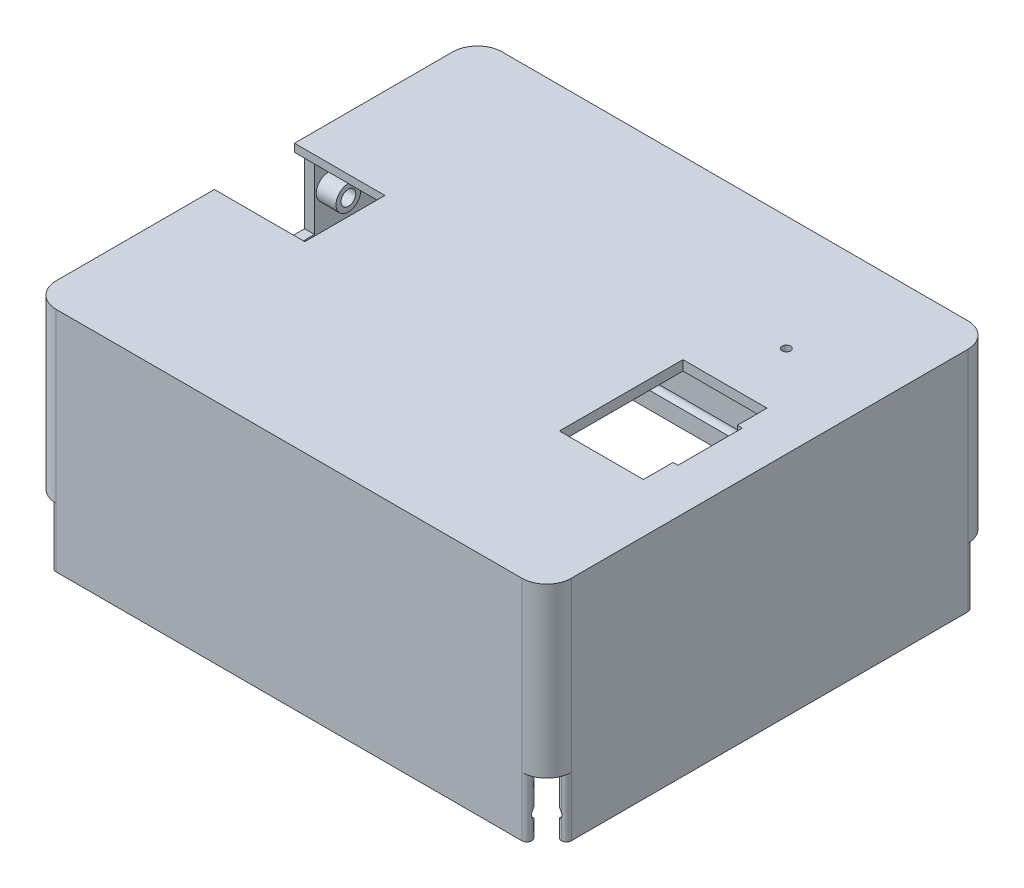
SolidWorks part; units mm, degrees
ref_plane "Plan de face" through (0, 0, 0) normal (0, 0, 1) x (1, 0, 0)
ref_plane "Plan de dessus" through (0, 0, 0) normal (0, 1, 0) x (1, 0, 0)
ref_plane "Plan de droite" through (0, 0, 0) normal (1, 0, 0) x (0, 0, -1)
sketch "Esquisse1" plane through (0, 0, 0) normal (0, 1, 0) x (1, 0, 0)
  line L1 (-52.1, -45.1) -> (52.1, -45.1)
  line L2 (-52.1, -45.1) -> (-52.1, 45.1)
  line L3 (-52.1, 45.1) -> (52.1, 45.1)
  line L4 (52.1, -45.1) -> (52.1, 45.1)
  line L5 (-52.1, -45.1) -> (52.1, 45.1) construction
  line L6 (-52.1, 45.1) -> (52.1, -45.1) construction
  point P0 (0, 0)
  dimension "D1" = 104.2
  dimension "D2" = 90.2
extrude "Boss.-Extru.1" add sketch "Esquisse1" along normal blind 2
sketch "Esquisse2" plane through (0, 0, 0) normal (0, -1, 0) x (1, 0, 0)
  line L8 (50.1, -43.1) -> (50.1, 43.1)
  line L9 (50.1, 43.1) -> (-50.1, 43.1)
  line L10 (-50.1, 43.1) -> (-50.1, -43.1)
  line L11 (-50.1, -43.1) -> (50.1, -43.1)
  line L12 (50.1, -43.1) -> (50.1, 43.1)
  line L13 (50.1, 43.1) -> (-50.1, 43.1)
  line L14 (-50.1, 43.1) -> (-50.1, -43.1)
  line L15 (-50.1, -43.1) -> (50.1, -43.1)
  line L16 (52.1, -45.1) -> (52.1, 45.1)
  line L17 (52.1, 45.1) -> (-52.1, 45.1)
  line L18 (-52.1, 45.1) -> (-52.1, -45.1)
  line L19 (-52.1, -45.1) -> (52.1, -45.1)
  line L20 (52.1, -45.1) -> (52.1, 45.1)
  line L21 (52.1, 45.1) -> (-52.1, 45.1)
  line L22 (-52.1, 45.1) -> (-52.1, -45.1)
  line L23 (-52.1, -45.1) -> (52.1, -45.1)
  dimension "D1" = 2
  dimension "D2" = 0
extrude "Boss.-Extru.2" add sketch "Esquisse2" along normal blind 44
sketch "Esquisse3" plane through (0, -44, 0) normal (0, -1, 0) x (1, 0, 0)
  line L0 (-50.1, 41.1) -> (-50.1, 43.1)
  line L1 (-52.1, 45.1) -> (-48.1, 45.1)
  line L2 (-52.1, 45.1) -> (-52.1, 41.1)
  line L3 (-52.1, 41.1) -> (-50.1, 41.1)
  line L4 (-48.1, 45.1) -> (-48.1, 43.1)
  line L5 (-50.1, 43.1) -> (-48.1, 43.1)
  dimension "D1" = 4
  dimension "D2" = 4
  dimension "D3" = 2
  dimension "D4" = 2
extrude "Enlèv. mat.-Extru.1" cut sketch "Esquisse3" against normal blind 12
mirror "Symétrie1" about plane through (0, 0, 0) normal (0, 0, 1) of "Enlèv. mat.-Extru.1"
mirror "Symétrie2" about plane through (0, 0, 0) normal (1, 0, 0) of "Symétrie1"
fillet "Congé3" radius 1 16 edges at (-48.1, -38, 45.1) (-48.1, -38, 43.1) (-50.1, -38, 41.1) (-52.1, -38, 41.1) (48.1, -38, 45.1) (48.1, -38, 43.1) (52.1, -38, 41.1) (50.1, -38, 41.1) (52.1, -38, -41.1) (50.1, -38, -41.1) (48.1, -38, -43.1) (48.1, -38, -45.1) (-48.1, -38, -45.1) (-48.1, -38, -43.1) (-50.1, -38, -41.1) (-52.1, -38, -41.1)
fillet "Congé1" radius 5 4 edges at (52.1, -15, 45.1) (52.1, -15, -45.1) (-52.1, -15, -45.1) (-52.1, -15, 45.1)
sketch "Esquisse4" plane through (0, 0, 0) normal (1, 0, 0) x (0, 0, -1)
  line L0 (-43.1, -32) -> (-43.1, -44) construction
  line L1 (-43.1, -38.4) -> (-43.1, -40.6)
  line L2 (-44.1, -44) -> (-43.1, -44) construction
  arc A1 (-43.1, -38.4) -> (-43.1, -40.6) centre (-43.1, -39.5) ccw
  dimension "D1" = 1.1
  dimension "D2" = 4.5
extrude "Enlèv. mat.-Extru.2" cut sketch "Esquisse4" against normal through all both and the other way through all
mirror "Symétrie4" about plane through (0, 0, 0) normal (0, 0, 1) of "Enlèv. mat.-Extru.2"
sketch "Esquisse5" plane through (0, 0, 0) normal (0, 0, 1) x (1, 0, 0)
  line L0 (-50.1, -32) -> (-50.1, -44) construction
  line L1 (-51.1, -44) -> (-50.1, -44) construction
  line L2 (-50.1, -38.4) -> (-50.1, -40.6)
  arc A0 (-50.1, -38.4) -> (-50.1, -40.6) centre (-50.1, -39.5) ccw
  dimension "D1" = 1.1
  dimension "D2" = 4.5
extrude "Enlèv. mat.-Extru.3" cut sketch "Esquisse5" against normal through all both and the other way through all
mirror "Symétrie5" about plane through (0, 0, 0) normal (1, 0, 0) of "Enlèv. mat.-Extru.3"
sketch "Esquisse6" plane through (-52.1, 0, 0) normal (-1, 0, 0) x (0, 0, 1)
  line L0 (0, 15.9382) -> (0, -19.3286) construction
  line L1 (-40.1, 2) -> (40.1, 2) construction
  line L2 (-10.15, -14) -> (10.15, -14)
  line L3 (-10.15, -14) -> (-10.15, 0)
  line L4 (-10.15, 0) -> (10.15, 0)
  line L5 (10.15, -14) -> (10.15, 0)
  line L6 (-10.15, -14) -> (10.15, 0) construction
  line L7 (-10.15, 0) -> (10.15, -14) construction
  point P3 (0, -7)
  dimension "D1" = 14
  dimension "D2" = 2
  dimension "D3" = 20.3
extrude "Enlèv. mat.-Extru.4" cut sketch "Esquisse6" against normal blind 5 and the other way through all
sketch "Esquisse7" plane through (-52.1, 0, 0) normal (-1, 0, 0) x (0, 0, 1)
  line L0 (0, 0) -> (0, 2) construction
  line L1 (-40.1, 2) -> (40.1, 2) construction
  line L3 (-8.1, 0) -> (8.1, 0)
  line L4 (-8.1, 0) -> (-8.1, 2)
  line L5 (-8.1, 2) -> (8.1, 2)
  line L6 (8.1, 0) -> (8.1, 2)
  line L7 (-8.1, 0) -> (8.1, 2) construction
  line L8 (-8.1, 2) -> (8.1, 0) construction
  point P7 (0, 1)
  dimension "D1" = 16.2
extrude "Enlèv. mat.-Extru.5" cut sketch "Esquisse7" against normal blind 18.3
sketch "Esquisse11" plane through (0, 0, 0) normal (0, 1, 0) x (1, 0, 0)
  line L0 (-52.1, 0) -> (-32.1, 0) construction
  line L1 (-52.1, 10.15) -> (-52.1, -10.15) construction
  line L3 (-52.1, 40.1) -> (-52.1, 8.1) construction
  line L4 (-52.1, -10.15) -> (-32.1, -10.15)
  line L5 (-52.1, -10.15) -> (-52.1, 10.15)
  line L6 (-52.1, 10.15) -> (-32.1, 10.15)
  line L7 (-32.1, -10.15) -> (-32.1, 10.15)
  line L8 (-52.1, -10.15) -> (-32.1, 10.15) construction
  line L9 (-52.1, 10.15) -> (-32.1, -10.15) construction
  point P6 (-42.1, 0)
  dimension "D1" = 20.3
  dimension "D2" = 20
extrude "Enlèv. mat.-Extru.8" cut sketch "Esquisse11" along normal blind 0.4
sketch "Esquisse15" plane through (0, -44, 0) normal (0, -1, 0) x (1, 0, 0)
  line L0 (-50.1, 40.1) -> (-50.1, -40.1) construction
  line L1 (50.3, -43.3) -> (-50.3, -43.3)
  line L2 (50.3, -43.3) -> (50.3, 43.3)
  line L3 (50.3, 43.3) -> (-50.3, 43.3)
  line L4 (-50.3, -43.3) -> (-50.3, 43.3)
  line L5 (50.3, -43.3) -> (-50.3, 43.3) construction
  line L6 (50.3, 43.3) -> (-50.3, -43.3) construction
  line L7 (47.1, 43.1) -> (-47.1, 43.1) construction
  point P0 (0, 0)
  dimension "D1" = 0.2
  dimension "D2" = 0.2
extrude "Enlèv. mat.-Extru.10" cut sketch "Esquisse15" against normal blind 4.5
sketch "Esquisse16" plane through (-52.1, 0, 0) normal (-1, 0, 0) x (0, 0, 1)
  circle A0 centre (-13, -7) radius 1.5
  dimension "D1" = 3
extrude "Enlèv. mat.-Extru.11" cut sketch "Esquisse16" against normal blind 4
mirror "Symétrie6" about plane through (0, 0, 0) normal (0, 0, 1) of "Enlèv. mat.-Extru.11"
sketch "Esquisse17" plane through (0, 2, 0) normal (0, 1, 0) x (1, 0, 0)
  line L0 (52.1, -40.1) -> (52.1, 40.1) construction
  line L1 (25.1, -15.5179) -> (42.1, -15.5179)
  line L2 (25.1, -15.5179) -> (25.1, 9.4821)
  line L3 (25.1, 9.4821) -> (42.1, 9.4821)
  line L4 (42.1, -15.5179) -> (42.1, 9.4821)
  line L5 (25.1, -15.5179) -> (42.1, 9.4821) construction
  line L6 (25.1, 9.4821) -> (42.1, -15.5179) construction
  point P0 (33.6, -3.0179)
  dimension "D1" = 25
  dimension "D2" = 17
  dimension "D3" = 10
extrude "Enlèv. mat.-Extru.12" cut sketch "Esquisse17" against normal up to next
sketch "Esquisse19" plane through (0, 0, 0) normal (0, -1, 0) x (1, 0, 0)
  line L0 (33.6, 19.5179) -> (33.6, -24.4821) construction
  line L8 (25.1, -9.4821) -> (25.1, 15.5179) construction
  line L9 (42.1, 15.5179) -> (42.1, -9.4821) construction
  line L10 (25.1, 15.5179) -> (42.1, 15.5179) construction
  line L11 (23.6, 7.9179) -> (46.6322, 7.9179) construction
  line L12 (42.1, -9.4821) -> (25.1, -9.4821) construction
  circle A0 centre (33.6, -21.8821) radius 0.85
  dimension "D1" = 1.7
  dimension "D2" = 1.5
  dimension "D5" = 7.6
  dimension "D7" = 12.4
extrude "Enlèv. mat.-Extru.13" cut sketch "Esquisse19" against normal blind 2
sketch "Esquisse20" plane through (-50.1, 0, 0) normal (1, 0, 0) x (0, 0, -1)
  circle A0 centre (-13, -7) radius 2.5
  circle A1 centre (13, -7) radius 2.5
  circle A2 centre (-13, -7) radius 1.5 construction
  circle A3 centre (-13, -7) radius 1.5
  circle A4 centre (13, -7) radius 1.5 construction
  circle A5 centre (13, -7) radius 1.5
  dimension "D1" = 5
  dimension "D2" = 5
extrude "Boss.-Extru.4" add sketch "Esquisse20" along normal blind 4
sketch "Esquisse21" plane through (0, 2, 0) normal (0, 1, 0) x (1, 0, 0)
  line L0 (25.1, -3.0179) -> (52.1, -3.0179) construction
  line L1 (25.1, 9.4821) -> (25.1, -15.5179) construction
  line L2 (52.1, -40.1) -> (52.1, 40.1) construction
  line L3 (42.1, -15.5179) -> (42.1, 9.4821) construction
  line L4 (43.1, -9.5179) -> (42.1, -9.5179)
  line L5 (43.1, -9.5179) -> (43.1, 3.4821)
  line L6 (43.1, 3.4821) -> (42.1, 3.4821)
  line L7 (42.1, -9.5179) -> (42.1, 3.4821)
  line L8 (43.1, -9.5179) -> (42.1, 3.4821) construction
  line L9 (43.1, 3.4821) -> (42.1, -9.5179) construction
  point P6 (42.6, -3.0179)
  dimension "D1" = 13
  dimension "D2" = 1
extrude "Enlèv. mat.-Extru.14" cut sketch "Esquisse21" against normal up to next
sketch "Esquisse22" plane through (0, 0, 0) normal (0, -1, 0) x (1, 0, 0)
  line L0 (33.6, 15.5179) -> (33.6, 26.6551) construction
  line L5 (25.1, 15.5179) -> (42.1, 15.5179) construction
  line L7 (21.6, 19.0179) -> (45.6, 19.0179)
  line L8 (21.6, 19.0179) -> (21.6, 21.0179)
  line L9 (21.6, 21.0179) -> (45.6, 21.0179)
  line L10 (45.6, 19.0179) -> (45.6, 21.0179)
  line L11 (21.6, 19.0179) -> (45.6, 21.0179) construction
  line L12 (21.6, 21.0179) -> (45.6, 19.0179) construction
  line L13 (21.6, 19.0179) -> (23, 19.0179)
  line L14 (21.6, 19.0179) -> (21.6, 13.5179)
  line L15 (21.6, 13.5179) -> (23, 13.5179)
  line L16 (23, 19.0179) -> (23, 13.5179)
  line L17 (45.6, 19.0179) -> (44.2, 19.0179)
  line L18 (45.6, 19.0179) -> (45.6, 13.5179)
  line L19 (45.6, 13.5179) -> (44.2, 13.5179)
  line L20 (44.2, 19.0179) -> (44.2, 13.5179)
  point P0 (33.6, 20.0179)
  dimension "D1" = 3.5
  dimension "D2" = 24
  dimension "D3" = 2
  dimension "D4" = 2
  dimension "D5" = 21.2
extrude "Boss.-Extru.5" add sketch "Esquisse22" along normal blind 2 contours L16 L7 L14 L15 | L7 L10 L9 L8 | L7 L20 L19 L18 region at (33.6, 0, 20.0179) region at (22.3, 0, 16.2679) region at (44.9, 0, 16.2679)
sketch "Esquisse25" plane through (0, -2, 0) normal (0, -1, 0) x (1, 0, 0)
  line L0 (25.1, 15.5179) -> (42.1, 15.5179) construction
  line L1 (21.6, 21.0179) -> (27.1, 21.0179)
  line L2 (21.6, 21.0179) -> (21.6, 13.5179)
  line L3 (21.6, 13.5179) -> (27.1, 13.5179)
  line L4 (27.1, 21.0179) -> (27.1, 13.5179)
  line L5 (33.6, 15.5179) -> (33.6, 10.1392) construction
  line L6 (45.6, 21.0179) -> (40.1, 21.0179)
  line L7 (45.6, 21.0179) -> (45.6, 13.5179)
  line L8 (45.6, 13.5179) -> (40.1, 13.5179)
  line L9 (40.1, 21.0179) -> (40.1, 13.5179)
  dimension "D1" = 2
  dimension "D2" = 13
extrude "Boss.-Extru.6" add sketch "Esquisse25" along normal blind 2
sketch "Esquisse26" plane through (0, 2, 0) normal (0, 1, 0) x (1, 0, 0)
  line L1 (19.3072, 26.5406) -> (47.2996, 26.5406)
  line L2 (19.3072, 26.5406) -> (19.3072, -21.6728)
  line L3 (19.3072, -21.6728) -> (47.2996, -21.6728)
  line L4 (47.2996, 26.5406) -> (47.2996, -21.6728)
  line L5 (-69.9367, 63.7848) -> (79.0025, 63.7848)
  line L6 (-69.9367, 63.7848) -> (-69.9367, -67.0226)
  line L7 (-69.9367, -67.0226) -> (79.0025, -67.0226)
  line L8 (79.0025, 63.7848) -> (79.0025, -67.0226)
extrude "Enlèv. mat.-Extru.15" [suppressed] cut sketch "Esquisse26" against normal through all
sketch "Esquisse27" plane through (0, 0, 0) normal (0, -1, 0) x (1, 0, 0)
  line L1 (17.4631, -12.015) -> (28.9063, -12.015)
  line L2 (17.4631, -12.015) -> (17.4631, -29.2136)
  line L3 (17.4631, -29.2136) -> (28.9063, -29.2136)
  line L4 (28.9063, -12.015) -> (28.9063, -29.2136)
  line L5 (50.2353, -12.015) -> (37.0993, -12.015)
  line L6 (50.2353, -12.015) -> (50.2353, -29.2136)
  line L7 (50.2353, -29.2136) -> (37.0993, -29.2136)
  line L8 (37.0993, -12.015) -> (37.0993, -29.2136)
extrude "Enlèv. mat.-Extru.16" [suppressed] cut sketch "Esquisse27" against normal through all
